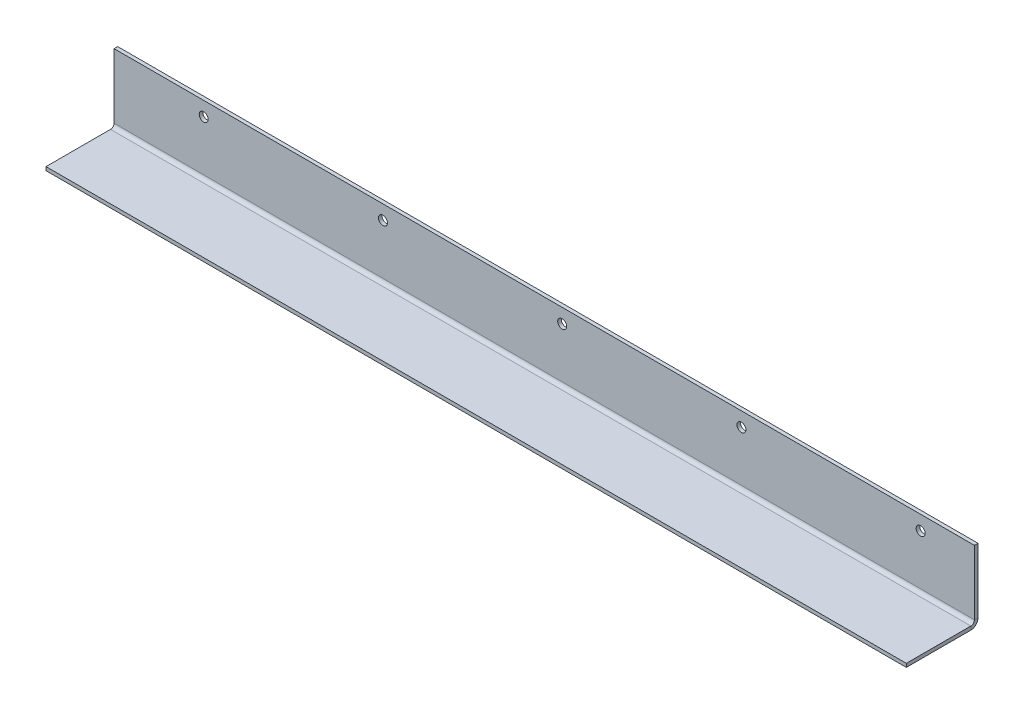
SolidWorks part; units mm, degrees
note: The reader was unsure of these and kept them because the rebuilt part matched: flange length of "Ребро-кромка1".
ref_plane "Спереди" through (0, 0, 0) normal (0, 0, 1) x (1, 0, 0)
ref_plane "Сверху" through (0, 0, 0) normal (0, 1, 0) x (1, 0, 0)
ref_plane "Справа" through (0, 0, 0) normal (1, 0, 0) x (0, 0, -1)
sketch "Эскиз1" plane through (0, 0, 0) normal (0, 1, 0) x (1, 0, 0)
  line L1 (0, 0) -> (480, 0)
  line L2 (0, 0) -> (0, 40)
  line L3 (0, 40) -> (480, 40)
  line L4 (480, 0) -> (480, 40)
base flange "Базовая кромка1" sketch "Эскиз1" thickness 2 reverse thickness direction no parameters "D1"=2
edge flange "Ребро-кромка1" sketch "Эскиз8" flange angle 90 flange length 40 flange position material inside bend radius 2 thickness 2 relief rectangular parameters "D6"=10
sketch "Эскиз8" plane through (0, 0, -40) normal (0, 0, -1) x (-1, 0, 0)
  line L0 (-480, 0) -> (0, 0) construction
  line L1 (-480, 0) -> (0, 0)
  line L2 (-480, 0) -> (-480, 38)
  line L3 (-480, 38) -> (0, 38)
  line L4 (0, 38) -> (0, 0)
bend "EdgeBend1" bend radius 2 bend angle 90 parameters "D5"=1
sketch "Эскиз9" plane through (0, 0, -40) normal (0, 0, -1) x (-1, 0, 0)
  circle A0 centre (-450, 30) radius 2.5
  circle A1 centre (-350, 30) radius 2.5
  circle A2 centre (-250, 30) radius 2.5
  circle A3 centre (-150, 30) radius 2.5
  circle A4 centre (-50, 30) radius 2.5
  dimension "D1" = 5
extrude "Вырез-Вытянуть1" cut sketch "Эскиз9" against normal through all normal cut yes
sketch "Сгиб-Линии1" [suppressed] plane through (0, 0, 0) normal (0, 1, 0) x (1, 0, 0)
sketch "Граничная рамка1" [suppressed] plane through (0, 0, 0) normal (0, 1, 0) x (1, 0, 0)
sheet metal parameters "Листовой металл1" thickness 2 parameters "D1"=2
flat pattern "Развертка1" [suppressed]
sketch "Сгиб-Линии2" plane through (0, 0, 0) normal (0, 1, 0) x (1, 0, 0)
sketch3d "Граничная рамка2" [suppressed]
  line L0 (-480, 80, 0) -> (0, 80, 0) construction
  line L1 (-480, 0, 0) -> (0, 0, 0) construction
  line L2 (-480, 80, 0) -> (-480, 0, 0) construction
  line L3 (0, 80, 0) -> (0, 0, 0) construction
sheet metal parameters "Листовой металл2" thickness 2 parameters "D1"=2
flat pattern "Развертка1"
sketch "Сгиб-Линии2" plane through (0, 0, 0) normal (0, 1, 0) x (1, 0, 0)
  line L0 (480, 78.3562) -> (0, 78.3562) construction
  line L1 (480, 78.3562) -> (0, 78.3562) construction
sketch3d "Граничная рамка2" [suppressed]
  line L0 (480, 156.7124, 0) -> (0, 156.7124, 0) construction
  line L1 (480, 0, 0) -> (0, 0, 0) construction
  line L2 (480, 156.7124, 0) -> (480, 0, 0) construction
  line L3 (0, 156.7124, 0) -> (0, 0, 0) construction
bend of the flat pattern "Плоское состояние-<EdgeBend1>1"
sheet metal parameters "Листовой металл3" thickness 2 parameters "D1"=2
flat pattern "Развертка1"
sketch "Сгиб-Линии2" plane through (0, 0, 0) normal (0, 1, 0) x (1, 0, 0)
  line L0 (480, 38.3562) -> (0, 38.3562) construction
  line L1 (480, 38.3562) -> (0, 38.3562) construction
sketch3d "Граничная рамка2" [suppressed]
  line L0 (480, 76.7124, 0) -> (0, 76.7124, 0) construction
  line L1 (480, 0, 0) -> (0, 0, 0) construction
  line L2 (480, 76.7124, 0) -> (480, 0, 0) construction
  line L3 (0, 76.7124, 0) -> (0, 0, 0) construction
bend of the flat pattern "Плоское состояние-<EdgeBend1>1"
